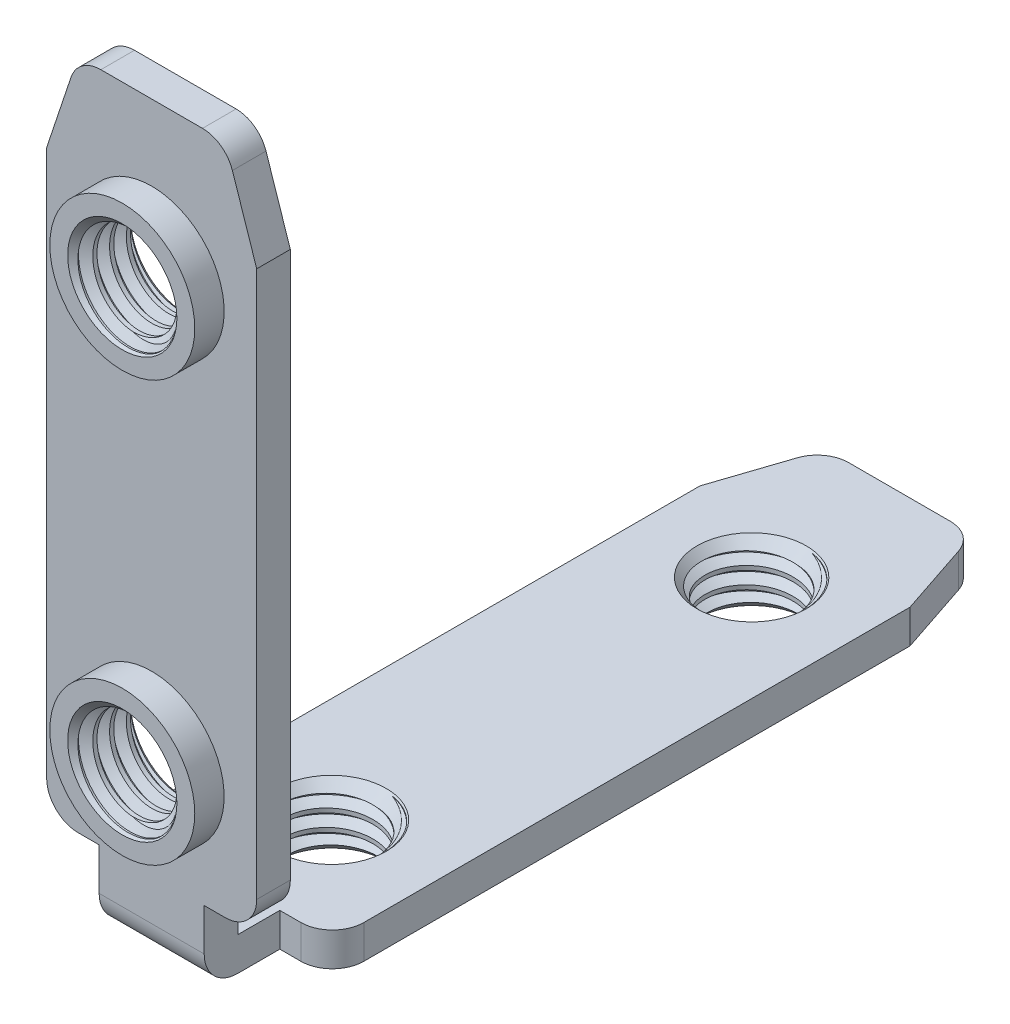
SolidWorks part; units mm, degrees
material "Plain Carbon Steel"
ref_plane "Front Plane" through (0, 0, 0) normal (0, 0, 1) x (1, 0, 0)
ref_plane "Top Plane" through (0, 0, 0) normal (0, 1, 0) x (1, 0, 0)
ref_plane "Right Plane" through (0, 0, 0) normal (1, 0, 0) x (0, 0, -1)
sketch "Sketch1" plane through (0, 0, 0) normal (0, 0, 1) x (1, 0, 0)
  line L0 (-10, 0) -> (0, 0) construction
  line L1 (0, 0) -> (0, 34) construction
  line L2 (-3.5, 2) -> (-2.5, 2)
  line L3 (-2.5, 2) -> (-2.5, 0)
  line L4 (-5, 3.5) -> (-5, 29.5)
  line L5 (-5, 29.5) -> (-3.8419, 32.9743)
  line L6 (-2.4189, 34) -> (2.4189, 34)
  line L7 (5, 29.5) -> (3.8419, 32.9743)
  line L8 (5, 3.5) -> (5, 29.5)
  line L9 (2.5, 2) -> (2.5, 0)
  line L10 (3.5, 2) -> (2.5, 2)
  line L11 (-2.5, 0) -> (2.5, 0)
  arc A0 (5, 3.5) -> (3.5, 2) centre (3.5, 3.5) cw
  arc A1 (-3.5, 2) -> (-5, 3.5) centre (-3.5, 3.5) cw
  arc A3 (-3.8419, 32.9743) -> (-2.4189, 34) centre (-2.4189, 32.5) cw
  arc A4 (3.8419, 32.9743) -> (2.4189, 34) centre (2.4189, 32.5) ccw
  point P16 (5, 2)
  point P19 (-5, 2)
  point P30 (-3.5, 34)
  point P33 (3.5, 34)
  dimension "D4" = 7
  dimension "D8" = 1.5
  dimension "D7" = 1.5
  dimension "D1" = 2
  dimension "D2" = 34
  dimension "D3" = 10
  dimension "D5" = 4.5
  dimension "D6" = 5
extrude "Boss-Extrude1" add sketch "Sketch1" along normal blind 1.6
sketch "Sketch2" plane through (0, 0, 1.6) normal (0, 0, 1) x (1, 0, 0)
  line L0 (-10, 0) -> (0, 0) construction
  line L2 (0, 0) -> (0, 34) construction
  line L3 (2.4189, 34) -> (-2.4189, 34) construction
  circle A0 centre (0, 6.96) radius 3.45
  circle A1 centre (0, 26.96) radius 3.45
  dimension "D1" = 6.9
  dimension "D3" = 6.96
  dimension "D2" = 20
extrude "Boss-Extrude2" add sketch "Sketch2" along normal blind 1.4
sketch "Sketch10" plane through (0, 0, 3) normal (0, 0, 1) x (1, 0, 0)
  circle A0 centre (0, 6.96) radius 2.1
  circle A1 centre (0, 26.96) radius 2.1
  circle A2 centre (0, 26.96) radius 3.45 construction
  circle A3 centre (0, 6.96) radius 3.45 construction
  dimension "D1" = 4.2
extrude "Cut-Extrude1" cut sketch "Sketch10" against normal through all
chamfer "Chamfer1" distance 0.5 angle 45 4 edges at (2.1, 6.96, 3) (2.1, 26.96, 3) (2.1, 6.96, 0) (2.1, 26.96, 0)
ref_plane "Plane1" through (0, 0, 0) normal (0, -0.7071, -0.7071) x (1, 0, 0)
sketch "Sketch5" plane through (2.5, 0, 0) normal (1, 0, 0) x (0, 0, -1)
  line L0 (0, 0) -> (-1.6, 0)
  line L1 (0, -1.6) -> (0, 0)
  arc A0 (-1.6, 0) -> (0, -1.6) centre (0, 0) ccw
extrude "Boss-Extrude3" add sketch "Sketch5" against normal up to surface (5 mm away) up to face at (-2.5, 1, 0.8)
mirror "Mirror4" about plane through (0, 0, 0) normal (0, -0.7071, -0.7071) of "Chamfer1", "Cut-Extrude1", "Boss-Extrude1", "Boss-Extrude2"
thread "Thread1" pitch 0.8 method cut profile "Thread Profile2" start angle 0, offset 1, length 5, pitch 0.8, diameter 4.2
ref_plane "Plane3" through (2.1, 26.96, -0.5) normal (0, -1, 0) x (1, 0, 0)
sketch "Thread Profile2" plane through (2.1, 26.96, -0.5) normal (0, -1, 0) x (1, 0, 0)
  line L0 (0, 0) -> (0, 0.8) construction
  line L1 (0, 0) -> (0.433, 0.25)
  line L2 (0.433, 0.25) -> (0.433, 0.35)
  line L3 (0.433, 0.35) -> (0, 0.6)
  line L4 (0.433, 0.3) -> (0, 0.3) construction
  line L11 (0, 0) -> (0, 0.6)
  point P2 (0, 0)
  dimension "Pitch" = 0.8
  dimension "Profile_Angle" = 60
  dimension "Profile_Land" = 0.1
  dimension "Profile_Height" = 0.433
thread "Thread2" pitch 0.8 method cut profile "Thread Profile3" start angle 0, offset 1, length 5, pitch 0.8, diameter 4.2
ref_plane "Plane4" through (2.1, 6.96, -0.5) normal (0, -1, 0) x (1, 0, 0)
sketch "Thread Profile3" plane through (2.1, 6.96, -0.5) normal (0, -1, 0) x (1, 0, 0)
  line L0 (0, 0) -> (0, 0.8) construction
  line L1 (0, 0) -> (0.433, 0.25)
  line L2 (0.433, 0.25) -> (0.433, 0.35)
  line L3 (0.433, 0.35) -> (0, 0.6)
  line L4 (0.433, 0.3) -> (0, 0.3) construction
  line L11 (0, 0) -> (0, 0.6)
  point P2 (0, 0)
  dimension "Pitch" = 0.8
  dimension "Profile_Angle" = 60
  dimension "Profile_Land" = 0.1
  dimension "Profile_Height" = 0.433
thread "Thread3" pitch 0.8 method cut profile "Thread Profile4" start angle 0, offset 1, length 5, pitch 0.8, diameter 4.2
ref_plane "Plane5" through (-2.1, 0.5, -6.96) normal (0, 0, 1) x (-1, 0, 0)
sketch "Thread Profile4" plane through (-2.1, 0.5, -6.96) normal (0, 0, 1) x (-1, 0, 0)
  line L0 (0, 0) -> (0, 0.8) construction
  line L1 (0, 0) -> (0.433, 0.25)
  line L2 (0.433, 0.25) -> (0.433, 0.35)
  line L3 (0.433, 0.35) -> (0, 0.6)
  line L4 (0.433, 0.3) -> (0, 0.3) construction
  line L11 (0, 0) -> (0, 0.6)
  point P2 (0, 0)
  dimension "Pitch" = 0.8
  dimension "Profile_Angle" = 60
  dimension "Profile_Land" = 0.1
  dimension "Profile_Height" = 0.433
thread "Thread4" pitch 0.8 method cut profile "Thread Profile5" start angle 0, offset 1, length 5, pitch 0.8, diameter 4.2
ref_plane "Plane6" through (-2.1, 0.5, -26.96) normal (0, 0, 1) x (-1, 0, 0)
sketch "Thread Profile5" plane through (-2.1, 0.5, -26.96) normal (0, 0, 1) x (-1, 0, 0)
  line L0 (0, 0) -> (0, 0.8) construction
  line L1 (0, 0) -> (0.433, 0.25)
  line L2 (0.433, 0.25) -> (0.433, 0.35)
  line L3 (0.433, 0.35) -> (0, 0.6)
  line L4 (0.433, 0.3) -> (0, 0.3) construction
  line L11 (0, 0) -> (0, 0.6)
  point P2 (0, 0)
  dimension "Pitch" = 0.8
  dimension "Profile_Angle" = 60
  dimension "Profile_Land" = 0.1
  dimension "Profile_Height" = 0.433
